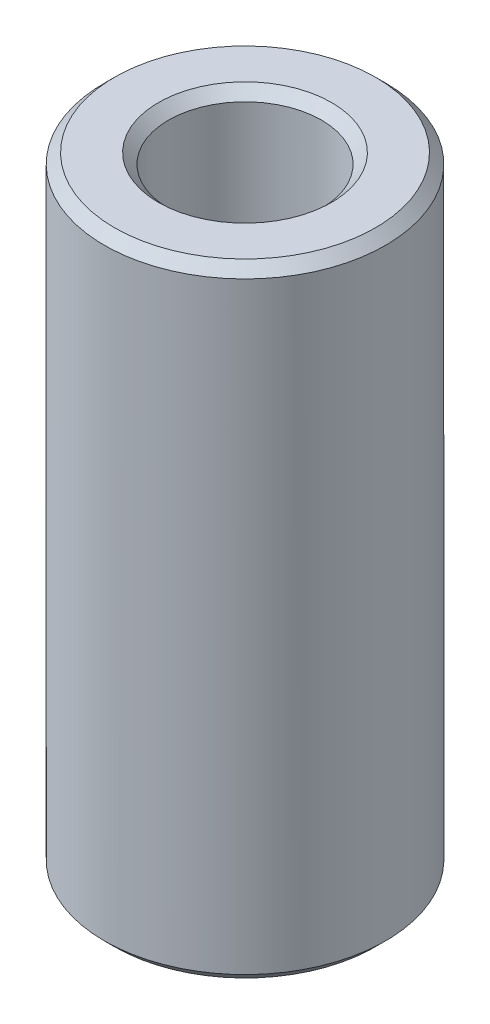
SolidWorks part; units mm, degrees
ref_plane "Front Plane" through (0, 0, 0) normal (0, 0, 1) x (1, 0, 0)
ref_plane "Top Plane" through (0, 0, 0) normal (0, 1, 0) x (1, 0, 0)
ref_plane "Right Plane" through (0, 0, 0) normal (1, 0, 0) x (0, 0, -1)
sketch "Sketch1" plane through (0, 0, 0) normal (0, 1, 0) x (1, 0, 0)
  circle A0 centre (0, 0) radius 50
  dimension "SLEEVE_OD" = 100
extrude "Boss-Extrude1" add sketch "Sketch1" along normal blind 221.4599
sketch "Sketch2" plane through (0, 0, 0) normal (0, 1, 0) x (1, 0, 0)
  circle A0 centre (0, 0) radius 27.1872
  dimension "BORE_D" = 54.3744
extrude "Cut-Extrude1" cut sketch "Sketch2" along normal through all
chamfer "Chamfer1" distance 3.6032 angle 45 4 edges at (0, 221.4599, 27.1872) (0, 0, 27.1872) (0, 0, 50) (0, 221.4599, 50)
